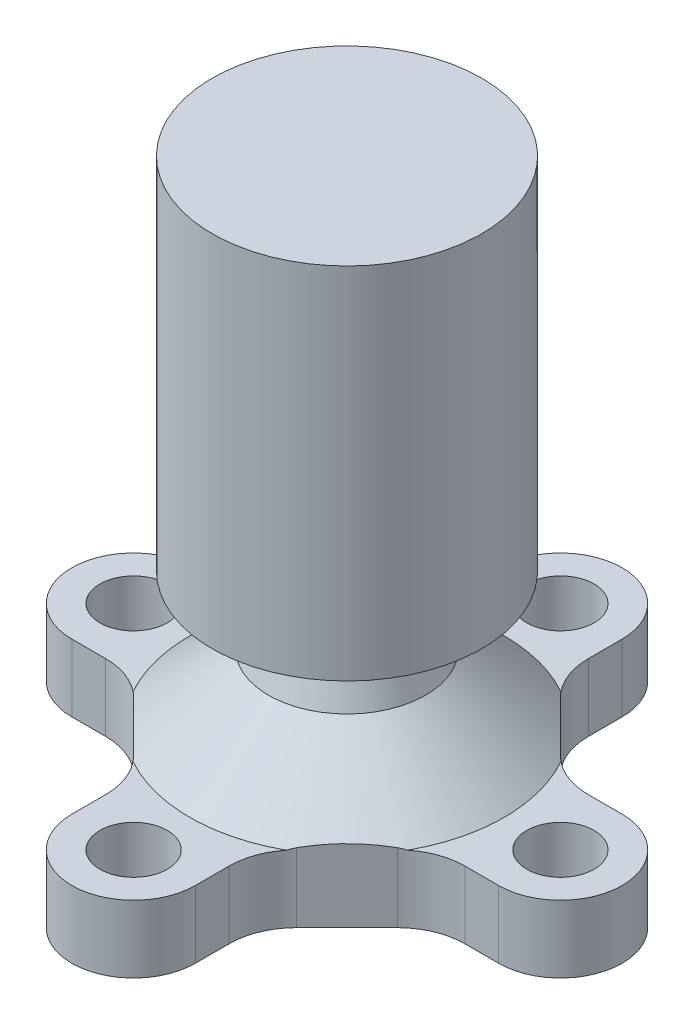
SolidWorks part; units mm, degrees
ref_plane "Front Plane" through (0, 0, 0) normal (0, 0, 1) x (1, 0, 0)
ref_plane "Top Plane" through (0, 0, 0) normal (0, 1, 0) x (1, 0, 0)
ref_plane "Right Plane" through (0, 0, 0) normal (1, 0, 0) x (0, 0, -1)
sketch "Sketch1" plane through (0, 0, 0) normal (0, 0, 1) x (1, 0, 0)
  line L0 (0, 0) -> (-19663.7468, 0) construction
  line L1 (0, 0) -> (0, 19663.7468) construction
  line L2 (-6, 25) -> (-6, 9)
  line L3 (-6, 9) -> (-2.5, 9)
  line L4 (-2.5, 9) -> (-3.5, 5.9603)
  line L5 (-3.5, 5.9603) -> (-7, 3)
  line L6 (-7, 3) -> (-13, 3)
  line L7 (-13, 3) -> (-13, 0)
  line L8 (-13, 0) -> (0, 0)
  line L9 (0, 0) -> (0, 25)
  line L12 (-6, 25) -> (0, 25)
  point P7 (0, 0)
  point P16 (0, 0)
  dimension "D2" = 25
  dimension "D3" = 6
  dimension "D4" = 13
  dimension "D8" = 16
  dimension "D9" = 6
  dimension "D10" = 3.2
  dimension "D11" = 3.5
  dimension "D12" = 3
  dimension "D13" = 2.5
revolve "Revolve2" add sketch "Sketch1" angle 360 about L1
sketch "Sketch2" plane through (0, 0, 0) normal (0, -1, 0) x (1, 0, 0)
  circle A0 centre (0, 0) radius 9.5 construction
  circle A1 centre (0, 9.5) radius 1.5
  circle A2 centre (9.5, 0) radius 1.5
  circle A3 centre (0, -9.5) radius 1.5
  circle A4 centre (-9.5, 0) radius 1.5
  point P14 (0, 0)
  dimension "D1" = 19
  dimension "D2" = 3
  dimension "D3" = 4
extrude "Cut-Extrude1" cut sketch "Sketch2" against normal blind 5
sketch "Sketch3" plane through (0, 0, 0) normal (0, -1, 0) x (1, 0, 0)
  line L0 (-9.5, 2.75) -> (-6.75, 2.75)
  line L1 (-6.75, 2.75) -> (-2.75, 6.75)
  line L2 (-2.75, 6.75) -> (-2.75, 9.5)
  line L3 (2.75, 9.5) -> (2.75, 6.75)
  line L4 (2.75, 6.75) -> (6.75, 2.75)
  line L5 (6.75, 2.75) -> (9.5, 2.75)
  line L6 (9.5, -2.75) -> (6.75, -2.75)
  line L7 (6.75, -2.75) -> (2.75, -6.75)
  line L8 (2.75, -6.75) -> (2.75, -9.5)
  line L9 (-2.75, -9.5) -> (-2.75, -6.75)
  line L10 (-2.75, -6.75) -> (-6.75, -2.75)
  line L11 (-6.75, -2.75) -> (-9.5, -2.75)
  arc A0 (2.75, 9.5) -> (-2.75, 9.5) centre (0, 9.5) ccw
  arc A1 (9.5, -2.75) -> (9.5, 2.75) centre (9.5, 0) ccw
  arc A2 (-2.75, -9.5) -> (2.75, -9.5) centre (0, -9.5) ccw
  arc A3 (-9.5, 2.75) -> (-9.5, -2.75) centre (-9.5, 0) ccw
  circle A4 centre (0, 0) radius 13 construction
  circle A5 centre (0, 0) radius 13
  point P12 (0, 0)
  point P30 (0, 0)
  circle M5 centre (0, 0) radius 13
  dimension "D1" = 5.5
  dimension "D2" = 4
  dimension "D3" = 4
extrude "Cut-Extrude2" cut sketch "Sketch3" against normal blind 5 contours A3 L0 L1 L2 A0 L3 L4 L5 A1 L6 L7 L8 A2 L9 L10 L11 M5 region at (-12.6323, 0, 0)
fillet "Fillet1" radius 3 8 edges at (-2.75, 1.5, 6.75) (-6.75, 1.5, 2.75) (-6.75, 1.5, -2.75) (-2.75, 1.5, -6.75) (2.75, 1.5, -6.75) (6.75, 1.5, -2.75) (6.75, 1.5, 2.75) (2.75, 1.5, 6.75)
